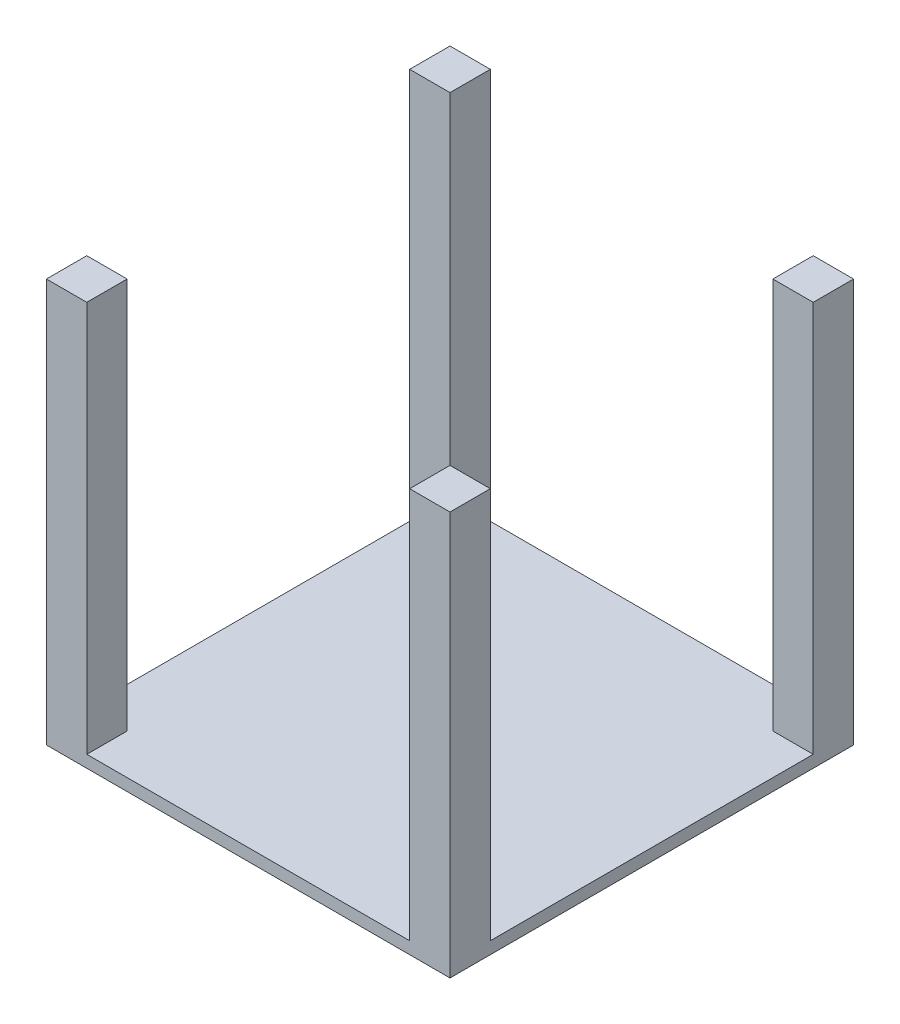
SolidWorks part; units mm, degrees
ref_plane "Front Plane" through (0, 0, 0) normal (0, 0, 1) x (1, 0, 0)
ref_plane "Top Plane" through (0, 0, 0) normal (0, 1, 0) x (1, 0, 0)
ref_plane "Right Plane" through (0, 0, 0) normal (1, 0, 0) x (0, 0, -1)
sketch "Sketch1" plane through (0, 0, 0) normal (0, 1, 0) x (1, 0, 0)
  line L1 (500, -500) -> (-500, -500)
  line L2 (500, -500) -> (500, 500)
  line L3 (500, 500) -> (-500, 500)
  line L4 (-500, -500) -> (-500, 500)
  line L5 (500, -500) -> (-500, 500) construction
  line L6 (500, 500) -> (-500, -500) construction
  line L7 (-500, 500) -> (-400, 500)
  line L8 (-500, 500) -> (-500, 400)
  line L9 (-500, 400) -> (-400, 400)
  line L10 (-400, 500) -> (-400, 400)
  line L11 (-450, 400) -> (-450, 500) construction
  line L12 (-500, 450) -> (-400, 450) construction
  line L13 (500, 500) -> (400, 500)
  line L14 (500, 500) -> (500, 400)
  line L15 (500, 400) -> (400, 400)
  line L16 (400, 500) -> (400, 400)
  line L17 (450, 400) -> (450, 500) construction
  line L18 (500, 450) -> (400, 450) construction
  line L19 (500, -500) -> (400, -500)
  line L20 (500, -500) -> (500, -400)
  line L21 (500, -400) -> (400, -400)
  line L22 (400, -500) -> (400, -400)
  line L23 (450, -400) -> (450, -500) construction
  line L24 (500, -450) -> (400, -450) construction
  line L25 (-500, -500) -> (-400, -500)
  line L26 (-500, -500) -> (-500, -400)
  line L27 (-500, -400) -> (-400, -400)
  line L28 (-400, -500) -> (-400, -400)
  line L29 (-450, -400) -> (-450, -500) construction
  line L30 (-500, -450) -> (-400, -450) construction
  point P0 (0, 0)
  point P83 (-450, -450)
  point P117 (-450, 450)
  point P148 (450, -450)
  point P353 (450, 450)
  dimension "D1" = 1000
  dimension "D2" = 1000
  dimension "D3" = 100
  dimension "D4" = 100
  dimension "D5" = 100
  dimension "D6" = 100
  dimension "D7" = 100
extrude "Boss-Extrude1" add sketch "Sketch1" along normal blind 30 contours L28 L1 L22 L21 L2 L15 L16 L3 L10 L9 L4 L27 region at (0, 0, 0)
extrude "Boss-Extrude2" add sketch "Sketch1<3>" along normal blind 1000 contours L1 L28 L27 L4 | L10 L3 L4 L9 | L3 L16 L15 L2 | L20 L21 L22 L19 region at (-450, 0, 450) region at (450, 0, -450) region at (-450, 0, -450)
sketch "Sketch1<3>" plane through (0, 0, 0) normal (0, 1, 0) x (1, 0, 0) same geometry as "Sketch1"
